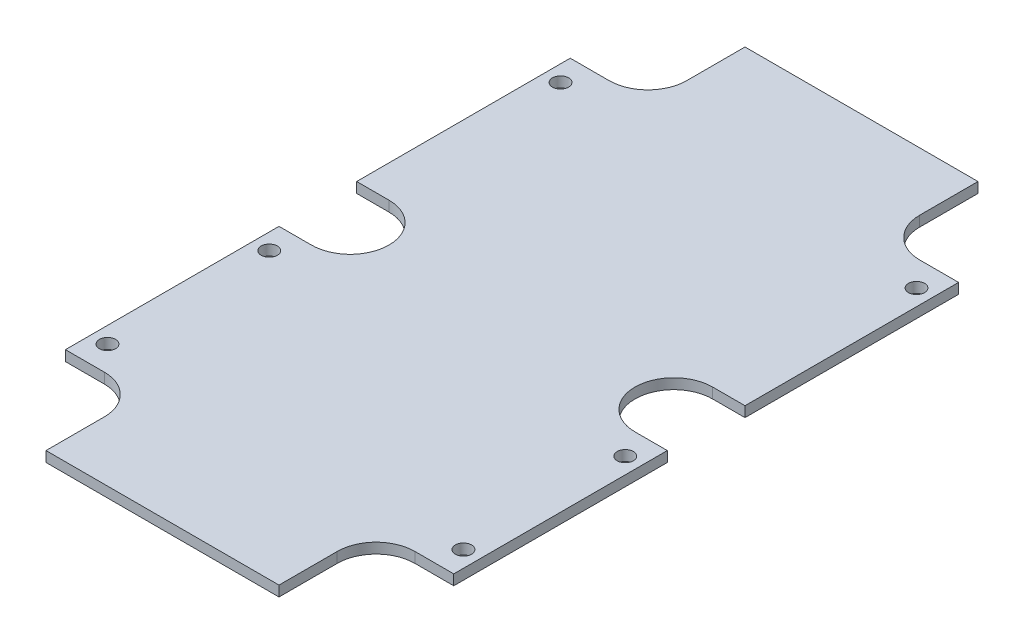
SolidWorks part; units mm, degrees
ref_plane "Front Plane" through (0, 0, 0) normal (0, 0, 1) x (1, 0, 0)
ref_plane "Top Plane" through (0, 0, 0) normal (0, 1, 0) x (1, 0, 0)
ref_plane "Right Plane" through (0, 0, 0) normal (1, 0, 0) x (0, 0, -1)
sketch "Sketch1" plane through (0, 0, 0) normal (0, 1, 0) x (1, 0, 0)
  line L0 (-30, -39) -> (-30, -6)
  line L5 (0, 54) -> (0, -54) construction
  line L6 (-19, 0) -> (19, 0) construction
  line L11 (-30, 39) -> (-24, 39)
  line L19 (30, 39) -> (24, 39)
  line L23 (-30, -6) -> (-25, -6)
  line L25 (-30, 6) -> (-25, 6)
  line L27 (-18, 54) -> (18, 54)
  line L28 (-18, 54) -> (-18, 45)
  line L29 (25, 6) -> (30, 6)
  line L31 (25, -6) -> (30, -6)
  line L33 (18, 54) -> (18, 45)
  line L35 (-30, -39) -> (-24, -39)
  line L41 (24, -39) -> (30, -39)
  line L47 (30, -39) -> (30, -6)
  line L48 (30, 6) -> (30, 39)
  line L49 (-30, 6) -> (-30, 39)
  line L51 (18, -45) -> (18, -54)
  line L52 (-18, -45) -> (-18, -54)
  line L53 (-18, -54) -> (18, -54)
  circle A6 centre (-27.5, -35) radius 1.25
  circle A7 centre (-27.5, -10) radius 1.25
  circle A8 centre (27.5, -10) radius 1.25
  circle A9 centre (27.5, -35) radius 1.25
  circle A10 centre (27.5, 35) radius 1.25
  circle A11 centre (-27.5, 35) radius 1.25
  arc A12 (-24, 39) -> (-18, 45) centre (-24, 45) ccw
  arc A13 (24, 39) -> (18, 45) centre (24, 45) cw
  arc A15 (25, 6) -> (25, -6) centre (25, 0) ccw
  arc A17 (-25, -6) -> (-25, 6) centre (-25, 0) ccw
  arc A18 (-18, -45) -> (-24, -39) centre (-24, -45) ccw
  arc A19 (24, -39) -> (18, -45) centre (24, -45) ccw
  point P0 (0, 0)
  point P2 (0, 0)
  dimension "D3" = 25
  dimension "D5" = 6
  dimension "D6" = 6
  dimension "D7" = 6
  dimension "D8" = 6
  dimension "D1" = 60
  dimension "D2" = 36
  dimension "D4" = 45
extrude "Boss-Extrude3" add sketch "Sketch1" along normal blind 1.6 contours L51 L53 L52 A18 L35 L0 L23 A17 L25 L49 L11 A12 L28 L27 L33 A13 L19 L48 L29 A15 L31 L47 L41 A19
extrude "Cut-Extrude2" cut sketch "Sketch1<9>" along normal blind 1.6 contours A10 | A11 | A9 | A8 | A7 | A6
sketch "Sketch1<9>" plane through (0, 0, 0) normal (0, 1, 0) x (1, 0, 0) same geometry as "Sketch1"
